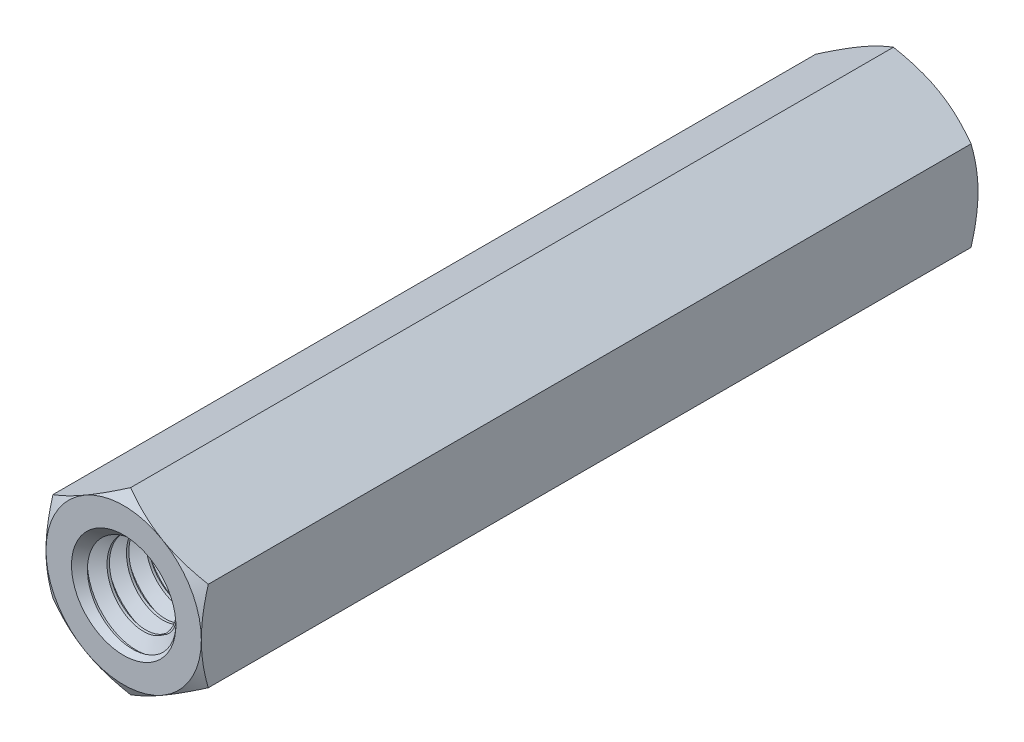
SolidWorks part; units mm, degrees
ref_plane "Front Plane" through (0, 0, 0) normal (0, 0, 1) x (1, 0, 0)
ref_plane "Top Plane" through (0, 0, 0) normal (0, 1, 0) x (1, 0, 0)
ref_plane "Right Plane" through (0, 0, 0) normal (1, 0, 0) x (0, 0, -1)
sketch "Sketch3" plane through (0, 0, 0) normal (1, 0, 0) x (0, 0, -1)
  line L0 (-15.875, 0) -> (15.875, 0) construction
  line L1 (0, 3.175) -> (0, -3.175) construction
  line L2 (-15.875, 2.0828) -> (-15.875, -2.0828) construction
  point P2 (6.35, 0)
  point P3 (-6.35, 0)
  dimension "Length" = 31.75
  dimension "Min Thread Length" = 9.525
  dimension "D1" = 9.525
  dimension "Thread Dia" = 4.1656
  dimension "Hex" = 6.35
sketch "Sketch1" plane through (0, 0, 0) normal (0, 0, 1) x (1, 0, 0)
  line L1 (0, 3.6662) -> (-3.175, 1.8331)
  line L2 (-3.175, 1.8331) -> (-3.175, -1.8331)
  line L3 (-3.175, -1.8331) -> (0, -3.6662)
  line L4 (0, -3.6662) -> (3.175, -1.8331)
  line L5 (3.175, -1.8331) -> (3.175, 1.8331)
  line L6 (3.175, 1.8331) -> (0, 3.6662)
  circle A0 centre (0, 0) radius 3.175 construction
  circle A1 centre (0, 0) radius 2.0828
extrude "Extrude1" add sketch "Sketch1" along normal up to vertex (15.875 mm away) and the other way up to vertex (15.875 mm away) up to point (0, 0, 15.875) other way up to point (0, 0, -15.875)
sketch "Sketch11" plane through (0, 0, -15.875) normal (0, 0, -1) x (-1, 0, 0)
  circle A0 centre (0, 0) radius 2.0828 construction
  circle A1 centre (0, 0) radius 2.0828
curve "Helix/Spiral1" pitch 0.7937 height 32.5437 radius 2.0828 centre (0, 0, -15.875) axis (0, 0, 1) start towards (0, 1, 0) parameters "Pitch"=0.7937
sketch "Sketch12" plane through (0, 0, 0) normal (1, 0, 0) x (0, 0, -1)
  line L0 (16.5695, 2.0828) -> (15.875, 2.0828)
  line L1 (16.5695, 2.0828) -> (16.2719, 1.5672)
  line L2 (16.2719, 1.5672) -> (16.1727, 1.5672)
  line L3 (16.1727, 1.5672) -> (15.875, 2.0828)
  line L4 (16.2223, 1.5672) -> (16.2223, 2.0828) construction
  line L5 (16.4207, 1.825) -> (16.0238, 1.825) construction
  dimension "D1" = 0.0992
  dimension "D2" = 0.3969
  dimension "D3" = 60
sweep "Sweep1" add profiles "Sketch12" path "Helix/Spiral1"
sketch "Sketch6" plane through (0, 0, -15.875) normal (0, 0, -1) x (-1, 0, 0)
  line L6 (0, 3.6662) -> (-3.175, 1.8331)
  line L7 (-3.175, 1.8331) -> (-3.175, -1.8331)
  line L8 (-3.175, -1.8331) -> (0, -3.6662)
  line L9 (0, -3.6662) -> (3.175, -1.8331)
  line L10 (3.175, -1.8331) -> (3.175, 1.8331)
  line L11 (3.175, 1.8331) -> (0, 3.6662)
  line L12 (0, 3.6662) -> (-3.175, 1.8331)
  line L13 (-3.175, 1.8331) -> (-3.175, -1.8331)
  line L14 (-3.175, -1.8331) -> (0, -3.6662)
  line L15 (0, -3.6662) -> (3.175, -1.8331)
  line L16 (3.175, -1.8331) -> (3.175, 1.8331)
  line L17 (3.175, 1.8331) -> (0, 3.6662)
  dimension "D1" = 0
extrude "Extrude2" cut sketch "Sketch6" along normal through all
sketch "Sketch7" plane through (0, 0, -15.875) normal (0, 0, -1) x (-1, 0, 0)
  circle A2 centre (0, 0) radius 2.1336
  circle A3 centre (0, 0) radius 2.1336
  dimension "D1" = 0.0508
extrude "Extrude3" cut sketch "Sketch7" against normal through all draft 43
sketch "Sketch8" plane through (0, 0, -15.875) normal (0, 0, -1) x (-1, 0, 0)
  circle A0 centre (0, 0) radius 3.175 construction
  circle A1 centre (0, 0) radius 3.175
extrude "Extrude4" cut sketch "Sketch8" against normal through all draft 60 flip side to cut
mirror "Mirror1" about plane through (0, 0, 0) normal (0, 0, 1) of "Extrude2", "Extrude3", "Extrude4"
sketch "Sketch9" plane through (0, 0, 0) normal (1, 0, 0) x (0, 0, -1)
  line L1 (-6.35, 2.1336) -> (6.35, 2.1336)
  line L2 (-6.35, 2.1336) -> (-6.35, 0)
  line L3 (-6.35, 0) -> (6.35, 0)
  line L4 (6.35, 2.1336) -> (6.35, 0)
  line L7 (-15.875, 0) -> (15.875, 0) construction
revolve "Revolve" add sketch "Sketch9" angle 360 about L0
sketch "Sketch10" plane through (0, 0, 0) normal (1, 0, 0) x (0, 0, -1)
  line L0 (15.875, 2.0828) -> (6.35, 2.0828)
  line L1 (-15.875, 2.0828) -> (-6.35, 2.0828)
  line L2 (6.35, 2.0828) -> (6.35, -2.0828)
  line L3 (-15.875, -2.1336) -> (-6.35, -2.1336)
  line L4 (-6.35, 2.0828) -> (-6.35, -2.1336)
  line L5 (6.35, -2.0828) -> (15.875, -2.0828)
equation "\"D1@Sketch3\" = \"Min Thread Length@Sketch3\""
equation "\"D3@Helix/Spiral1\" = \"Length@Sketch3\"+\"Pitch@Helix/Spiral1\""
equation "\"D1@Sketch12\" = \"Pitch@Helix/Spiral1\"*.125"
equation "\"D2@Sketch12\" = \"Pitch@Helix/Spiral1\"*.5"
